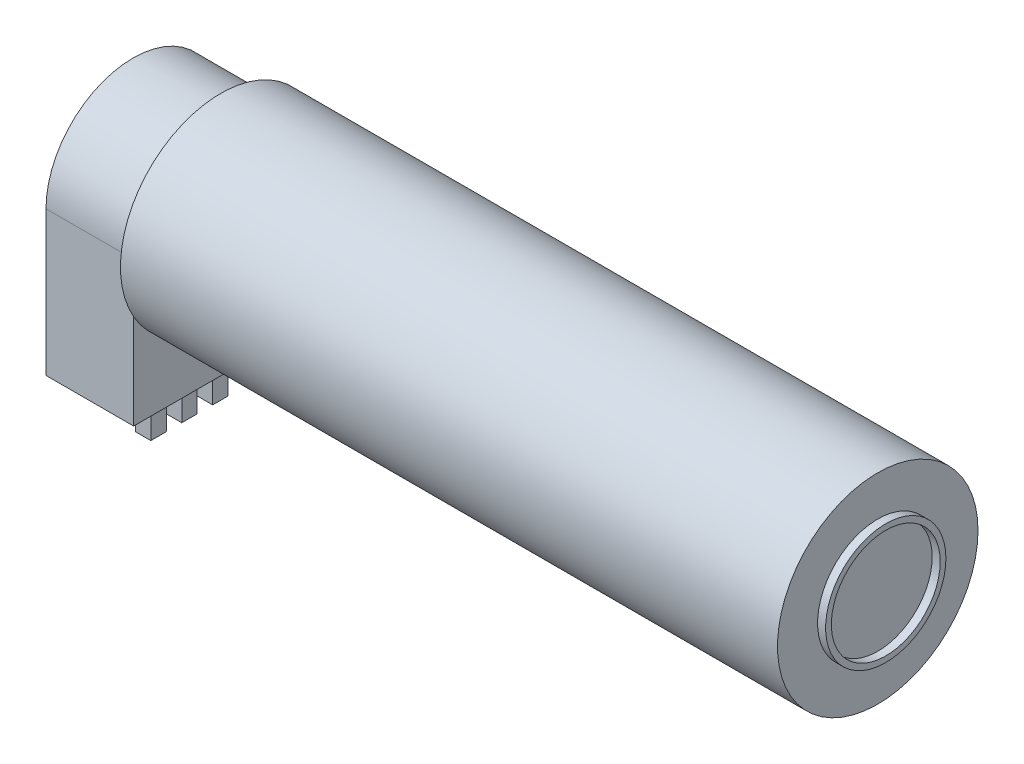
SolidWorks part; units mm, degrees
ref_plane "前视基准面" through (0, 0, 0) normal (0, 0, 1) x (1, 0, 0)
ref_plane "上视基准面" through (0, 0, 0) normal (0, 1, 0) x (1, 0, 0)
ref_plane "右视基准面" through (0, 0, 0) normal (1, 0, 0) x (0, 0, -1)
sketch "草图2" plane through (0, 0, 0) normal (1, 0, 0) x (0, 0, -1)
  circle A0 centre (0, 0) radius 17.5
  dimension "D1" = 35
extrude "凸台-拉伸1" add sketch "草图2" along normal blind 114.7
sketch "草图3" plane through (114.7, 0, 0) normal (1, 0, 0) x (0, 0, -1)
  circle A0 centre (0, 0) radius 10.5
  circle A1 centre (0, 0) radius 9.5
  dimension "D1" = 21
  dimension "D2" = 19
extrude "凸台-拉伸2" add sketch "草图3" along normal blind 1.4
sketch "草图6" plane through (0, 0, 0) normal (-1, 0, 0) x (0, 0, 1)
  line L0 (-15.2, 0) -> (-15.2, -25.2)
  line L1 (-15.2, -25.2) -> (15.2, -25.2)
  line L2 (15.2, -25.2) -> (15.2, 0)
  arc A0 (15.2, 0) -> (-15.2, 0) centre (0, 0) ccw
  dimension "D1" = 30.4
  dimension "D2" = 25.2
extrude "凸台-拉伸6" add sketch "草图6" along normal blind 15.3
sketch "草图8" plane through (0, -25.2, 0) normal (0, -1, 0) x (1, 0, 0)
  line L0 (-15.3, -15.2) -> (-15.3, 15.2) construction
  line L1 (-6, -4.6) -> (-5.3, -4.6)
  line L2 (-6, -4.6) -> (-6, -3.9)
  line L3 (-6, -3.9) -> (-5.3, -3.9)
  line L4 (-5.3, -4.6) -> (-5.3, -3.9)
  line L5 (-6, -4.6) -> (-5.3, -3.9) construction
  line L6 (-6, -3.9) -> (-5.3, -4.6) construction
  line L7 (-7, -2.9) -> (-7, -0.2)
  line L8 (-7, -5.6) -> (-4.3, -5.6)
  line L9 (-7, -5.6) -> (-7, -2.9)
  line L10 (-7, -2.9) -> (-4.3, -2.9)
  line L11 (-4.3, -5.6) -> (-4.3, -2.9)
  line L12 (-7, -5.6) -> (-4.3, -2.9) construction
  line L13 (-7, -2.9) -> (-4.3, -5.6) construction
  line L14 (-7, -2.9) -> (-4.3, -2.9)
  line L15 (-4.3, -2.9) -> (-4.3, -0.2)
  line L16 (-7, -0.2) -> (-4.3, -0.2)
  line L17 (-6, -1.2) -> (-5.3, -1.2)
  line L18 (-6, -1.9) -> (-6, -1.2)
  line L19 (-6, -1.9) -> (-5.3, -1.9)
  line L20 (-5.3, -1.9) -> (-5.3, -1.2)
  line L21 (-7, -0.2) -> (-7, 2.5)
  line L22 (-7, -0.2) -> (-4.3, -0.2)
  line L23 (-4.3, -0.2) -> (-4.3, 2.5)
  line L24 (-7, 2.5) -> (-4.3, 2.5)
  line L25 (-6, 1.5) -> (-5.3, 1.5)
  line L26 (-6, 0.8) -> (-6, 1.5)
  line L27 (-6, 0.8) -> (-5.3, 0.8)
  line L28 (-5.3, 0.8) -> (-5.3, 1.5)
  line L29 (-7, 2.5) -> (-7, 5.2)
  line L30 (-7, 2.5) -> (-4.3, 2.5)
  line L31 (-4.3, 2.5) -> (-4.3, 5.2)
  line L32 (-7, 5.2) -> (-4.3, 5.2)
  line L33 (-6, 4.2) -> (-5.3, 4.2)
  line L34 (-6, 3.5) -> (-6, 4.2)
  line L35 (-6, 3.5) -> (-5.3, 3.5)
  line L36 (-5.3, 3.5) -> (-5.3, 4.2)
  line L37 (-7, 5.2) -> (-7, 7.9)
  line L38 (-7, 5.2) -> (-4.3, 5.2)
  line L39 (-4.3, 5.2) -> (-4.3, 7.9)
  line L40 (-7, 7.9) -> (-4.3, 7.9)
  line L41 (-6, 6.9) -> (-5.3, 6.9)
  line L42 (-6, 6.2) -> (-6, 6.9)
  line L43 (-6, 6.2) -> (-5.3, 6.2)
  line L44 (-5.3, 6.2) -> (-5.3, 6.9)
  line L45 (-15.3, -15.2) -> (0, -15.2) construction
  point P0 (-5.65, -4.25)
  point P7 (-5.65, -4.25)
  dimension "D1" = 0.7
  dimension "D2" = 0.7
  dimension "D3" = 9.65
  dimension "D4" = 2.7
  dimension "D5" = 2.7
  dimension "D7" = 9.6
  dimension "D6" = 5
extrude "凸台-拉伸7" add sketch "草图8" along normal blind 8 contours L40 L39 L38 L37 | L21 L24 L23 L22 | L9 L10 L11 L8
extrude "凸台-拉伸8" add sketch "草图8<3>" along normal blind 2 contours L17 L20 L19 L18 | L33 L36 L35 L34
sketch "草图8<3>" plane through (0, -25.2, 0) normal (0, -1, 0) x (1, 0, 0) same geometry as "草图8"
